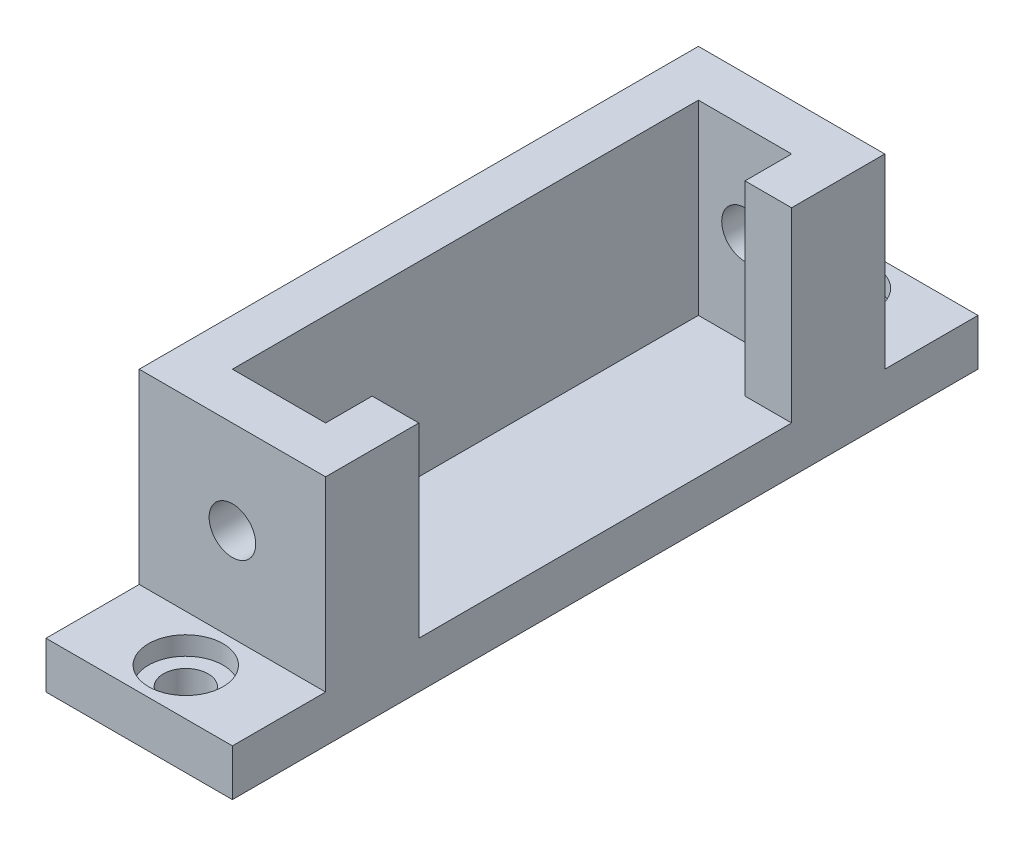
SolidWorks part; units mm, degrees
ref_plane "Plan de face" through (0, 0, 0) normal (0, 0, 1) x (1, 0, 0)
ref_plane "Plan de dessus" through (0, 0, 0) normal (0, 1, 0) x (1, 0, 0)
ref_plane "Plan de droite" through (0, 0, 0) normal (1, 0, 0) x (0, 0, -1)
sketch "Esquisse1" plane through (0, 0, 0) normal (0, 0, 1) x (1, 0, 0)
  line L0 (-19.9427, 10) -> (0.0573, 10)
  line L5 (-7.5427, 10) -> (-19.9427, 10)
  line L6 (0.0573, 10) -> (0.0573, 35)
  line L7 (0.0573, 35) -> (-19.9427, 35)
  line L8 (-19.9427, 10) -> (-19.9427, 35)
  line L9 (-7.5427, 8) -> (-12.3427, 8)
  line L10 (-7.5427, 8) -> (-7.5427, 10)
  line L11 (-7.5427, 10) -> (-12.3427, 10)
  line L16 (-12.3427, 8) -> (-12.3427, 10)
  circle A0 centre (-9.9427, 8) radius 2.4
  dimension "D4" = 2
  dimension "D1" = 4.8
  dimension "D2" = 25
  dimension "D3" = 20
  dimension "D5" = 7.6
extrude "Boss.-Extru.1" add sketch "Esquisse1" along normal blind 60 contours L8 L5 L6 L7 | L11 A0 | L9 A0 L11 | A0 L10 L5 | A0 L5 L16 | L9 A0 region at (-9.9427, 22.5178, 0) region at (-12.0383, 9.5251, 0) region at (-9.9427, 10.1612, 0) region at (-9.9427, 8.9198, 0) region at (-9.9427, 6.9814, 0) region at (-7.847, 9.5251, 0)
sketch "Esquisse2" plane through (0, 35, 0) normal (0, 1, 0) x (1, 0, 0)
  line L1 (-19.9427, 0) -> (0.0573, 0)
  line L2 (-14.9427, -5) -> (-14.9427, -55)
  line L3 (-14.9427, -55) -> (-4.9427, -55)
  line L4 (0.0573, 0) -> (-19.9427, 0)
  line L5 (-19.9427, 0) -> (-19.9427, -60)
  line L6 (0.0573, 0) -> (-19.9427, 0)
  line L7 (0.0573, -60) -> (0.0573, 0)
  line L9 (-19.9427, 0) -> (-19.9427, -60)
  line L11 (0.0573, -60) -> (0.0573, 0)
  line L12 (-4.9427, -55) -> (-4.9427, -5)
  line L13 (-4.9427, -5) -> (-14.9427, -5)
  line L14 (-19.9427, 0) -> (-19.9427, -10)
  line L15 (-19.9427, -10) -> (0.0573, -10)
  line L16 (0.0573, 0) -> (0.0573, -10)
  line L17 (-19.9427, -60) -> (0.0573, -60)
  line L18 (0.0573, 0) -> (-19.9427, 0) construction
  line L19 (-19.9427, -60) -> (0.0573, -60) construction
  line L20 (-19.9427, -60) -> (0.0573, -60)
  line L21 (-19.9427, -60) -> (0.0573, -60)
  line L22 (-19.9427, -60) -> (-19.9427, -50)
  line L23 (-19.9427, -50) -> (0.0573, -50)
  line L24 (0.0573, -60) -> (0.0573, -50)
  line M8 (0.0573, -60) -> (0.0573, 0)
  dimension "D2" = 10
  dimension "D4" = 10
  dimension "D1" = 0
  dimension "D3" = 5
extrude "Enlèv. mat.-Extru.1" cut sketch "Esquisse2" against normal blind 20 contours L3 L12 L2 | L12 L2 | L12 M8 | L12 L13 L2 region at (-2.4427, 35, 30) region at (-9.9427, 35, 30) region at (-9.9427, 35, 7.5) region at (-9.9427, 35, 52.5)
sketch "Esquisse3" plane through (0, 0, 5) normal (0, 0, 1) x (1, 0, 0)
  line L0 (-14.9427, 15) -> (-4.9427, 35)
  line L4 (-4.9427, 35) -> (-14.9427, 35)
  line L5 (-14.9427, 35) -> (-14.9427, 15)
  line L6 (-14.9427, 15) -> (-4.9427, 15)
  line L7 (-4.9427, 15) -> (-4.9427, 35)
  line L8 (-4.9427, 35) -> (-14.9427, 35)
  line L9 (-14.9427, 35) -> (-14.9427, 15)
  line L10 (-14.9427, 15) -> (-4.9427, 15)
  line L11 (-4.9427, 15) -> (-4.9427, 35)
  circle A0 centre (-9.9427, 25) radius 2.5
  dimension "D2" = 5
  dimension "D1" = 0
extrude "Enlèv. mat.-Extru.2" cut sketch "Esquisse3" against normal through all both and the other way through all contours L0 A0 | L0 A0 region at (-10.8917, 25.4745, 5) region at (-8.9937, 24.5255, 5)
sketch "Esquisse4" plane through (0, 0, 60) normal (0, 0, 1) x (1, 0, 0)
  line L5 (-19.9427, 10) -> (0.0573, 10)
  line L6 (-19.9427, 10) -> (-19.9427, 15)
  line L7 (-19.9427, 15) -> (0.0573, 15)
  line L8 (-19.9427, 35) -> (-19.9427, 10)
  line L9 (-19.9427, 10) -> (-12.3427, 10)
  line L10 (0.0573, 10) -> (0.0573, 35)
  line L17 (-7.5427, 10) -> (0.0573, 10)
  line L18 (-7.5427, 10) -> (0.0573, 10)
  line L33 (0.0573, 35) -> (-19.9427, 35)
  line L34 (-19.9427, 35) -> (-19.9427, 10)
  line L35 (-19.9427, 10) -> (-12.3427, 10)
  line L36 (0.0573, 10) -> (0.0573, 35)
  line L37 (0.0573, 35) -> (-19.9427, 35)
  line L42 (0.0573, 10) -> (0.0573, 15)
  line L43 (-12.3427, 10) -> (-12.3427, 8)
  line L44 (-12.3427, 10) -> (-12.3427, 8)
  line L45 (-7.5427, 8) -> (-7.5427, 10)
  line L46 (-7.5427, 8) -> (-7.5427, 10)
  arc A4 (-12.3427, 8) -> (-7.5427, 8) centre (-9.9427, 8) ccw
  arc A5 (-12.3427, 8) -> (-7.5427, 8) centre (-9.9427, 8) ccw
  dimension "D2" = 0
  dimension "D3" = 5
extrude "Boss.-Extru.2" add sketch "Esquisse4" along normal blind 10 contours L5 L36 L7 L6 region at (-9.9427, 12.5, 60)
ref_plane "Plan1" through (0, 0, 30) normal (0, 0, 1) x (1, 0, 0)
mirror "Symétrie1" about plane through (0, 0, 30) normal (0, 0, 1) of "Boss.-Extru.2"
sketch "Esquisse5" plane through (0, 15, 0) normal (0, 1, 0) x (1, 0, 0)
  line L16 (0.0573, -60) -> (-19.9427, -60) construction
  line L17 (-19.9427, -60) -> (-19.9427, -70) construction
  line L18 (-19.9427, -70) -> (0.0573, -70) construction
  line L19 (0.0573, -70) -> (0.0573, -60) construction
  line L20 (-19.9427, 0) -> (0.0573, 0) construction
  line L21 (0.0573, 0) -> (0.0573, 10) construction
  line L22 (0.0573, 10) -> (-19.9427, 10) construction
  line L23 (-19.9427, 10) -> (-19.9427, 0) construction
  line L24 (0.0573, -60) -> (-19.9427, -60)
  line L25 (-19.9427, -60) -> (-19.9427, -70)
  line L26 (-19.9427, -70) -> (0.0573, -70)
  line L27 (0.0573, -70) -> (0.0573, -60)
  line L28 (-19.9427, 0) -> (0.0573, 0)
  line L29 (0.0573, 0) -> (0.0573, 10)
  line L30 (0.0573, 10) -> (-19.9427, 10)
  line L31 (-19.9427, 10) -> (-19.9427, 0)
  line L32 (-19.9427, 10) -> (0, 0)
  line L33 (0.0573, -60) -> (-19.9427, -70)
  point P5 (-9.9713, 5)
  point P7 (-9.9427, -65)
hole_wizard "Chambrage pour vis à six pans creux M41" positions "Esquisse3D1" profile "Esquisse6" counterbore size "M4" standard "ISO" end condition through all
sketch3d "Esquisse3D1"
  point P0 (-9.9713, 15, -5)
  point P3 (-9.9427, 15, 65)
sketch "Esquisse6" plane through (-9.9713, 15, -5) normal (1, 0, 0) x (0, 0, 1)
  line L0 (0, 0) -> (0, 9.4)
  line L1 (0, 9.4) -> (2.4, 9.4)
  line L3 (2.4, 9.4) -> (2.4, 2)
  line L4 (2.4, 2) -> (4, 2)
  line L5 (4, 2) -> (4, 0)
  line L7 (4, 0) -> (0, 0)
  line L11 (0, -6.35) -> (0, 107.95) construction
  dimension "Diamètre du perçage jusqu'au prochain" = 4.8
  dimension "Profondeur du perçage jusqu'au prochain" = 9.4
  dimension "Diamètre du chambrage" = 8
  dimension "Profondeur du chambrage" = 2
